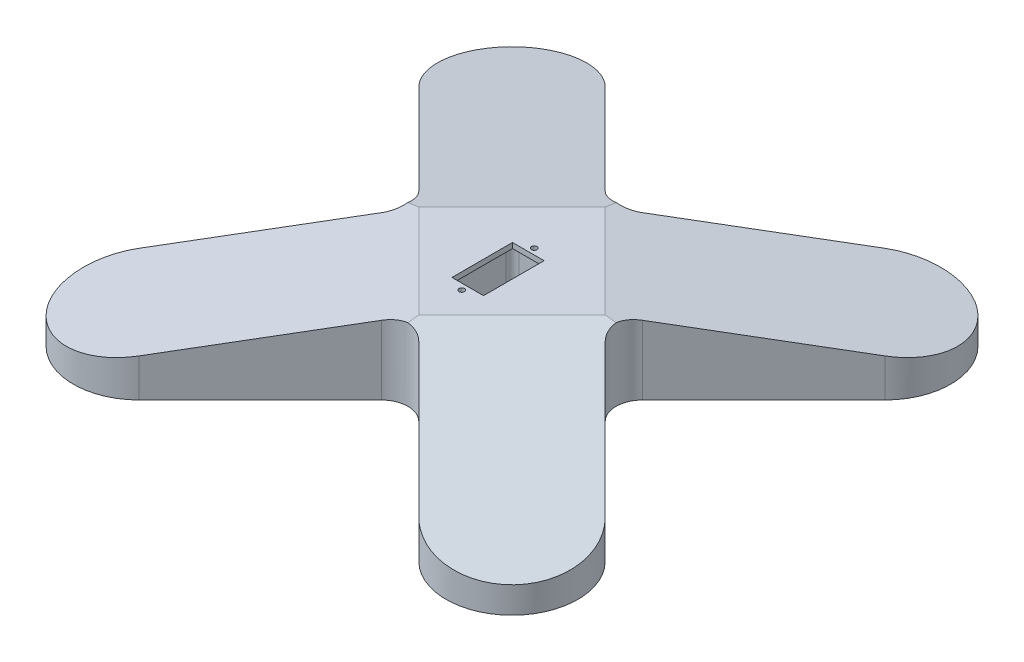
SolidWorks part; units mm, degrees
ref_plane "Front Plane" through (0, 0, 0) normal (0, 0, 1) x (1, 0, 0)
ref_plane "Top Plane" through (0, 0, 0) normal (0, 1, 0) x (1, 0, 0)
ref_plane "Right Plane" through (0, 0, 0) normal (1, 0, 0) x (0, 0, -1)
sketch "Sketch1" plane through (0, 0, 0) normal (0, 1, 0) x (1, 0, 0)
  line L0 (0, 35.3553) -> (53.033, 88.3883)
  line L1 (0, 0) -> (88.3883, 88.3883) construction
  line L2 (0, 0) -> (-76.2969, 0) construction
  line L3 (35.3553, 0) -> (88.3883, 53.033)
  line L4 (0, -35.3553) -> (53.033, -88.3883)
  line L5 (35.3553, 0) -> (88.3883, -53.033)
  line L6 (-35.3553, 0) -> (-88.3883, -53.033)
  line L7 (0, -35.3553) -> (-53.033, -88.3883)
  line L8 (0, 35.3553) -> (-53.033, 88.3883)
  line L9 (-35.3553, 0) -> (-88.3883, 53.033)
  arc A0 (53.033, 88.3883) -> (88.3883, 53.033) centre (70.7107, 70.7107) cw
  arc A1 (88.3883, -53.033) -> (53.033, -88.3883) centre (70.7107, -70.7107) cw
  arc A2 (-53.033, -88.3883) -> (-88.3883, -53.033) centre (-70.7107, -70.7107) cw
  arc A3 (-88.3883, 53.033) -> (-53.033, 88.3883) centre (-70.7107, 70.7107) cw
  point P27 (0, 0)
  dimension "D4" = 25
  dimension "D1" = 75
  dimension "D2" = 125
  dimension "D3" = 25
  dimension "D5" = 135
  dimension "D6" = 4
extrude "Boss-Extrude2" add sketch "Sketch1" along normal blind 28
sketch "Sketch3" plane through (0, 28, 0) normal (0, 1, 0) x (1, 0, 0)
  line L0 (0, 35.3553) -> (0, -35.3553) construction
  line L1 (-35.3553, 0) -> (35.3553, 0) construction
  line L2 (-5.99, -16.8) -> (5.99, -16.8)
  line L3 (-5.99, -16.8) -> (-5.99, 6.18)
  line L4 (-5.99, 6.18) -> (5.99, 6.18)
  line L5 (5.99, -16.8) -> (5.99, 6.18)
  line L6 (-5.99, -16.8) -> (5.99, 6.18) construction
  line L7 (-5.99, 6.18) -> (5.99, -16.8) construction
  line L8 (-5.99, -5.31) -> (5.99, -5.31) construction
  circle A0 centre (0, 8.47) radius 1.05
  circle A1 centre (0, 0) radius 3.75 construction
  circle A2 centre (0, -19.09) radius 1.05
  point P4 (0, -5.31)
  dimension "D4" = 2.1
  dimension "D6" = 7.5
  dimension "D1" = 11.98
  dimension "D2" = 22.98
  dimension "D3" = 8.47
  dimension "D5" = 2.29
extrude "Cut-Extrude1" cut sketch "Sketch3" against normal blind 28
sketch "Sketch4" plane through (0, 0, 0) normal (0, -1, 0) x (1, 0, 0)
  line L0 (0, 35.3553) -> (53.033, 88.3883) construction
  line L1 (-7.5, -42.8553) -> (7.5, -42.8553)
  line L2 (-7.5, -42.8553) -> (-7.5, -16.18)
  line L3 (-7.5, 42.8553) -> (7.5, 42.8553)
  line L4 (7.5, -42.8553) -> (7.5, -16.18)
  line L5 (-7.5, -42.8553) -> (7.5, 42.8553) construction
  line L6 (-7.5, 42.8553) -> (7.5, -42.8553) construction
  line L7 (-7.5, 26.8) -> (7.5, 26.8)
  line L8 (7.5, -16.18) -> (-7.5, -16.18)
  line L9 (5.99, -6.18) -> (-5.99, -6.18) construction
  line L10 (-5.99, 16.8) -> (5.99, 16.8) construction
  line L11 (-7.5, 26.8) -> (-7.5, 42.8553)
  line L12 (7.5, 26.8) -> (7.5, 42.8553)
  line L13 (-7.5, 26.8) -> (-15.99, 26.8)
  line L14 (-15.99, 26.8) -> (-15.99, -16.18)
  line L15 (-15.99, -16.18) -> (-7.5, -16.18)
  line L16 (7.5, -16.18) -> (15.99, -16.18)
  line L17 (15.99, -16.18) -> (15.99, 26.8)
  line L18 (15.99, 26.8) -> (7.5, 26.8)
  line L19 (-5.99, -6.18) -> (-5.99, 16.8) construction
  point P0 (0, 0)
  circle M13 centre (0, 19.09) radius 1.05
  circle M14 centre (0, -8.47) radius 1.05
  line M15 (5.99, 16.8) -> (5.99, -6.18)
  line M16 (5.99, -6.18) -> (-5.99, -6.18)
  line M17 (-5.99, -6.18) -> (-5.99, 16.8)
  line M18 (-5.99, 16.8) -> (5.99, 16.8)
  line M19 (-53.033, -88.3883) -> (0, -35.3553)
  line M20 (0, -35.3553) -> (53.033, -88.3883)
  dimension "D1" = 15
  dimension "D2" = 10
  dimension "D3" = 10
  dimension "D4" = 10
extrude "Cut-Extrude2" cut sketch "Sketch4" against normal blind 25 contours L17 L18 L7 L13 L14 L15 L8 L16 M14 M18 M15 M16 M17 M13 region at (-11.745, 0, -15.6443)
extrude "Cut-Extrude4" cut sketch "Sketch4<4>" against normal blind 10 contours L4 L8 L2 M19 M20 region at (0, 0, -27.7449)
sketch "Sketch4<4>" plane through (0, 0, 0) normal (0, -1, 0) x (1, 0, 0) same geometry as "Sketch4"
sketch "Sketch5" plane through (17.6777, 0, -17.6777) normal (0.7071, 0, -0.7071) x (-0.7071, 0, -0.7071)
  line L0 (-25, 28) -> (-125, 10)
  line L1 (-125, 28) -> (-125, 0) construction
  line L2 (-125, 0) -> (-100, 0) construction
  line L3 (-125, 10) -> (-125, 28)
  line L4 (-125, 28) -> (-25, 28)
  dimension "D1" = 10
extrude "Cut-Extrude5" cut sketch "Sketch5" against normal up to next
ref_plane "Plane1" through (0, 0, 0) normal (0.7071, 0, -0.7071) x (-0.7071, 0, -0.7071)
sketch "Sketch6" plane through (0, 0, 0) normal (0.7071, 0, -0.7071) x (-0.7071, 0, -0.7071)
  line L0 (0, -17.0528) -> (0, 46.2281) construction
  point P3 (0, 0)
pattern_circular "CirPattern1" count 4 over 360 about axis through (0, -17.0528, 0) along (0, 1, 0) of "Cut-Extrude5" reverse direction yes
fillet "Fillet1" radius 10 4 edges at (0, 19, -35.3553) (35.3553, 14, 0) (0, 14, 35.3553) (-35.3553, 14, 0)
chamfer "Chamfer1" distance 1 angle 45 10 edges at (0, 25, -16.18) (-15.99, 25, 5.31) (0, 25, 26.8) (15.99, 25, 5.31) (0, 25, 18.04) (-5.99, 25, 5.31) (0, 25, -6.18) (5.99, 25, 5.31) (0, 25, 16.8) (0, 25, -9.52)
fillet "Fillet2" radius 2.5 8 edges at (7.5, 5, -42.8553) (-7.5, 5, -42.8553) (-7.5, 5, -16.18) (7.5, 5, -16.18) (15.99, 12, -16.18) (-15.99, 12, -16.18) (15.99, 12, 26.8) (-15.99, 12, 26.8)
